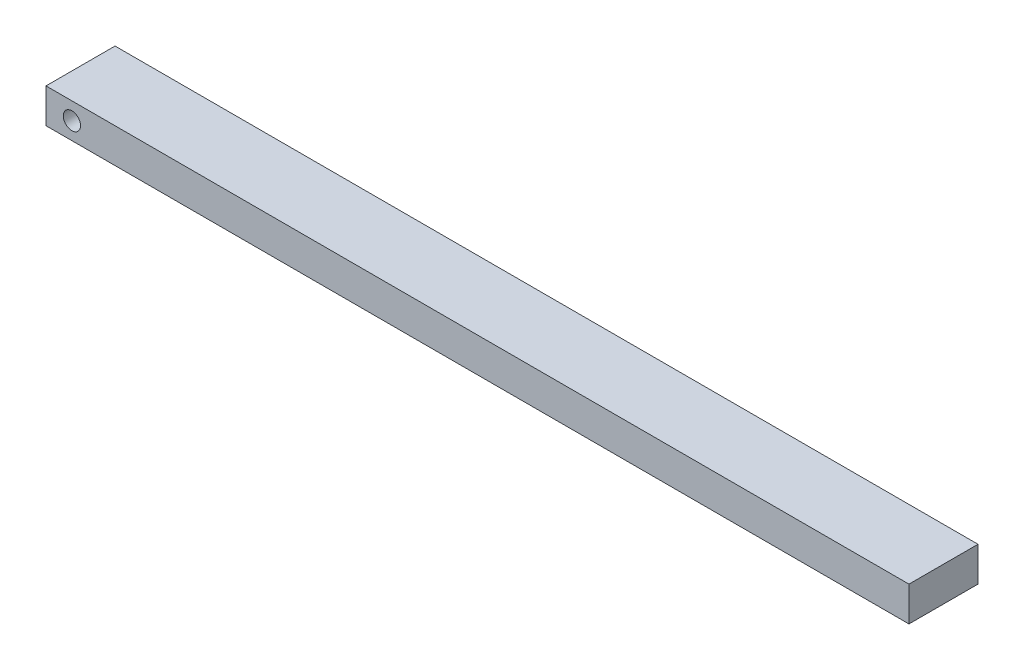
SolidWorks part; units mm, degrees
ref_plane "Front Plane" through (0, 0, 0) normal (0, 0, 1) x (1, 0, 0)
ref_plane "Top Plane" through (0, 0, 0) normal (0, 1, 0) x (1, 0, 0)
ref_plane "Right Plane" through (0, 0, 0) normal (1, 0, 0) x (0, 0, -1)
sketch "Sketch1" plane through (0, 0, 0) normal (0, 0, 1) x (1, 0, 0)
  line L0 (0, 10) -> (500, 10) construction
  line L1 (0, 0) -> (500, 0)
  line L2 (0, 0) -> (0, 20)
  line L3 (0, 20) -> (500, 20)
  line L4 (500, 0) -> (500, 20)
  circle A0 centre (15, 10) radius 5
  dimension "D3" = 15
  dimension "D1" = 20
  dimension "D2" = 500
extrude "Boss-Extrude1" add sketch "Sketch1" against normal blind 40
